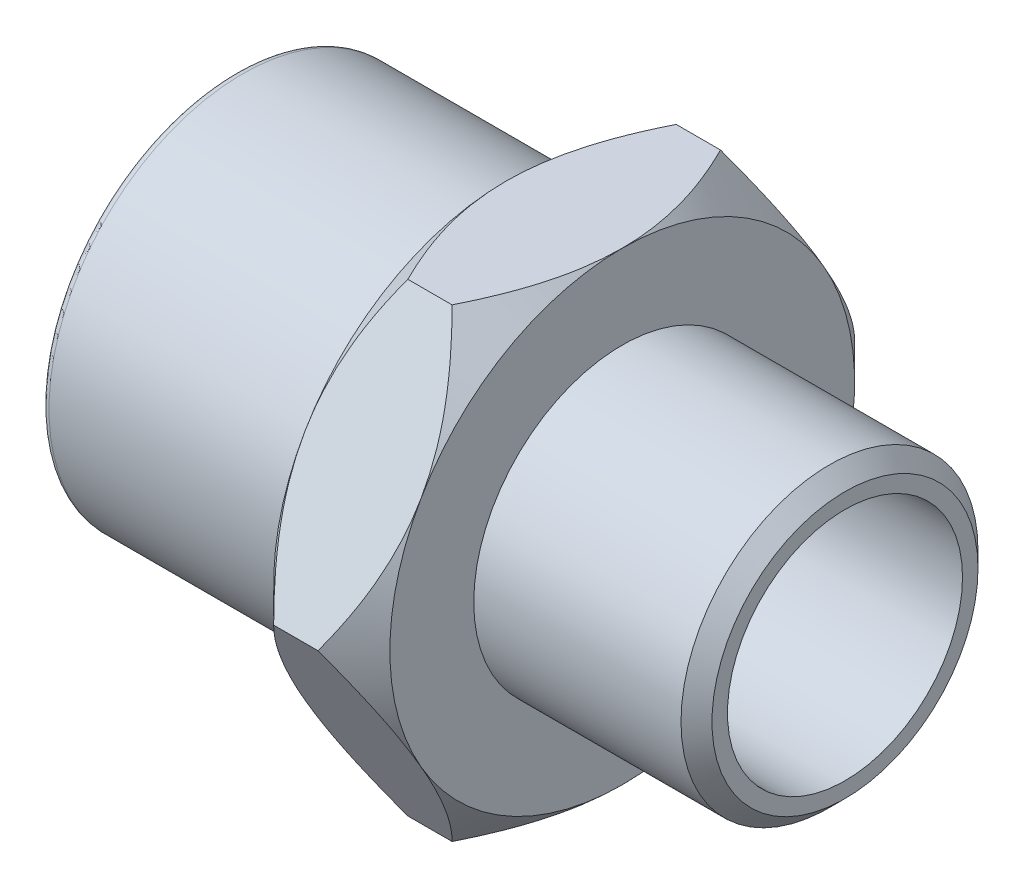
SolidWorks part; units mm, degrees
material "PE Высокой плотности"
ref_plane "Спереди" through (0, 0, 0) normal (0, 0, 1) x (1, 0, 0)
ref_plane "Сверху" through (0, 0, 0) normal (0, 1, 0) x (1, 0, 0)
ref_plane "Справа" through (0, 0, 0) normal (1, 0, 0) x (0, 0, -1)
sketch "Эскиз1" plane through (0, 0, 0) normal (1, 0, 0) x (0, 0, -1)
  line L1 (17.3205, 0) -> (8.6603, 15)
  line L2 (8.6603, 15) -> (-8.6603, 15)
  line L3 (-8.6603, 15) -> (-17.3205, 0)
  line L4 (-17.3205, 0) -> (-8.6603, -15)
  line L5 (-8.6603, -15) -> (8.6603, -15)
  line L6 (8.6603, -15) -> (17.3205, 0)
  circle A0 centre (0, 0) radius 15 construction
  dimension "Dгайки" = 30
extrude "Бобышка-Вытянуть1" add sketch "Эскиз1" against normal blind 7.5
sketch "Эскиз2" plane through (0, 0, 0) normal (1, 0, 0) x (0, 0, -1)
  circle A0 centre (0, 0) radius 15 construction
  circle A1 centre (0, 0) radius 15
extrude "Вырез-Вытянуть1" cut sketch "Эскиз2" against normal blind 20 draft 45 flip side to cut
sketch "Эскиз3" plane through (-7.5, 0, 0) normal (-1, 0, 0) x (0, 0, 1)
  circle A0 centre (0, 0) radius 15 construction
  circle A1 centre (0, 0) radius 15
extrude "Вырез-Вытянуть2" cut sketch "Эскиз3" against normal blind 20 draft 45 flip side to cut
sketch "Эскиз4" plane through (0, 0, 0) normal (1, 0, 0) x (0, 0, -1)
  circle A0 centre (0, 0) radius 12.5
  dimension "Dнаруж" = 25
extrude "Бобышка-Вытянуть2" add sketch "Эскиз4" against normal blind 25
sketch "Эскиз5" plane through (-25, 0, 0) normal (-1, 0, 0) x (0, 0, 1)
  circle A0 centre (0, 0) radius 10
  circle A1 centre (0, 0) radius 12.5 construction
  dimension "Dвнутр" = 20
extrude "Вырез-Вытянуть3" cut sketch "Эскиз5" against normal up to surface (17.5 mm away) up to face at (-7.5, 0, -12.5)
sketch "Эскиз6" plane through (0, 0, 0) normal (1, 0, 0) x (0, 0, -1)
  circle A0 centre (0, 0) radius 9.585
  circle A1 centre (0, 0) radius 15 construction
  dimension "Dрезьбы" = 19.17
extrude "Бобышка-Вытянуть3" add sketch "Эскиз6" along normal blind 14.3775
chamfer "Фаска1" distance 1 angle 45 1 edges at (14.3775, 0, -9.585)
fillet "Скругление1" radius 0.5 2 edges at (-25, 0, -12.5) (-25, 0, 10)
sketch3d "Трехмерный эскиз1"
  line L0 (0, 0, 0) -> (-25, 0, 0) construction
  point P6 (-7.5, 0, 0)
other "Точка соединения1" parameters "Диаметр"=20, "StubLength"=0
ref_axis "Ось1" through (-17.5, 0, 0) along (1, 0, 0)
sketch "Эскиз7" plane through (14.3775, 0, 0) normal (1, 0, 0) x (0, 0, -1)
  circle A2 centre (0, 0) radius 7.585
  circle A3 centre (0, 0) radius 7.585
  dimension "D1" = 1
extrude "Вырез-Вытянуть4" cut sketch "Эскиз7" against normal up to surface (21.8775 mm away) up to face at (-7.5, 0, -12.5)
equation "\"D1@Бобышка-Вытянуть1\"=1/4 * \"Dгайки@Эскиз1\""
equation "\"D1@Бобышка-Вытянуть2\"= \"Dнаруж@Эскиз4\""
equation "\"D1@Бобышка-Вытянуть3\"=0.75* \"Dрезьбы@Эскиз6\""
